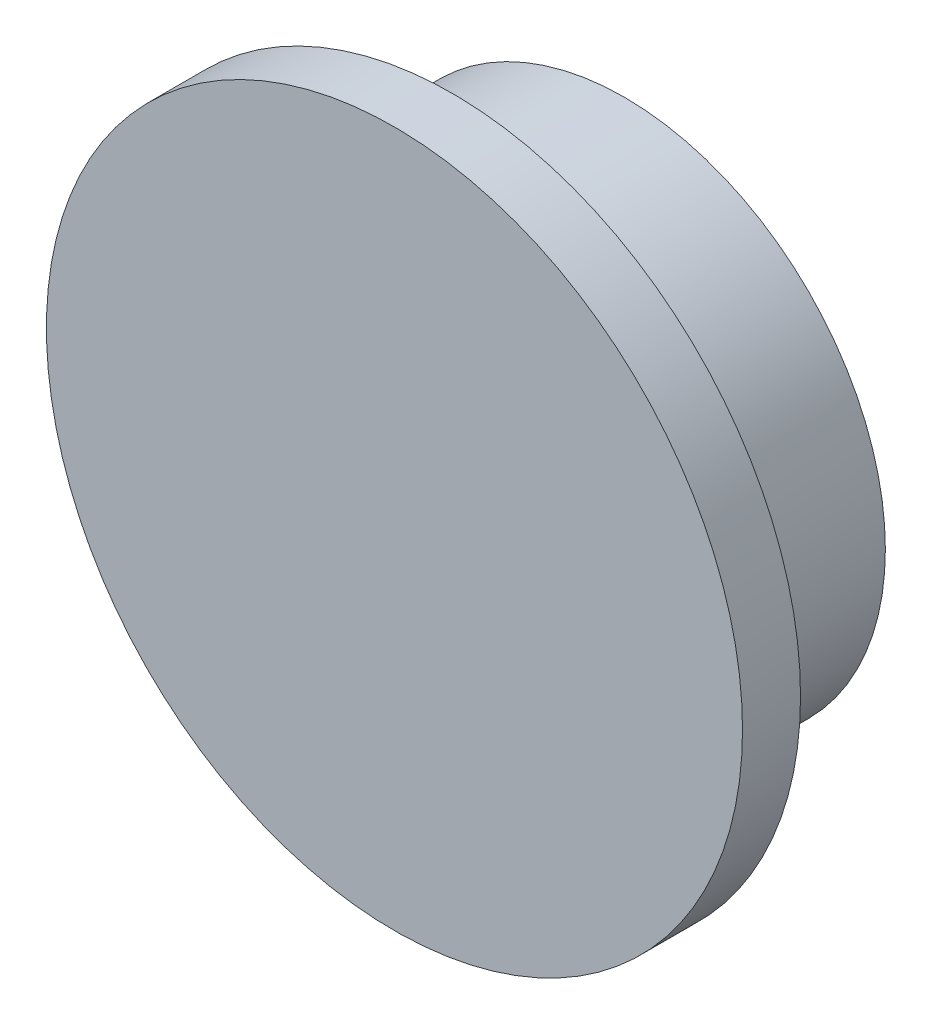
SolidWorks part; units mm, degrees
ref_plane "前视基准面" through (0, 0, 0) normal (0, 0, 1) x (1, 0, 0)
ref_plane "上视基准面" through (0, 0, 0) normal (0, 1, 0) x (1, 0, 0)
ref_plane "右视基准面" through (0, 0, 0) normal (1, 0, 0) x (0, 0, -1)
sketch "草图1" plane through (0, 0, 0) normal (0, 0, 1) x (1, 0, 0)
  circle A0 centre (-38.7348, 8.307) radius 22.5
  circle A1 centre (-38.5481, 8.6803) radius 5
extrude "凸台-拉伸1" add sketch "草图1" along normal blind 15
sketch "草图2" plane through (0, 0, 15) normal (0, 0, 1) x (1, 0, 0)
  circle A0 centre (-38.5481, 8.6803) radius 30
extrude "凸台-拉伸2" add sketch "草图2" along normal blind 5
thread "螺纹线1" pitch 0.3175 method cut profile "螺纹线轮廓1" start angle 0, offset 0, length 10, pitch 0.3175, diameter 10
ref_plane "基准面4" through (-33.5481, 8.6803, 0) normal (0, -1, 0) x (1, 0, 0)
sketch "螺纹线轮廓1" plane through (-33.5481, 8.6803, 0) normal (0, -1, 0) x (1, 0, 0)
  line L0 (0, 0) -> (0, 0.3175) construction
  line L1 (0, 0) -> (0.1719, 0.0992)
  line L2 (0.1719, 0.0992) -> (0.1719, 0.1389)
  line L3 (0.1719, 0.1389) -> (0, 0.2381)
  line L4 (0.1719, 0.1191) -> (0, 0.1191) construction
  line L11 (0, 0) -> (0, 0.2381)
  point P2 (0, 0)
  dimension "Pitch" = 0.3175
  dimension "Profile_Angle" = 60
  dimension "Profile_Land" = 0.0397
  dimension "Profile_Height" = 0.1719
